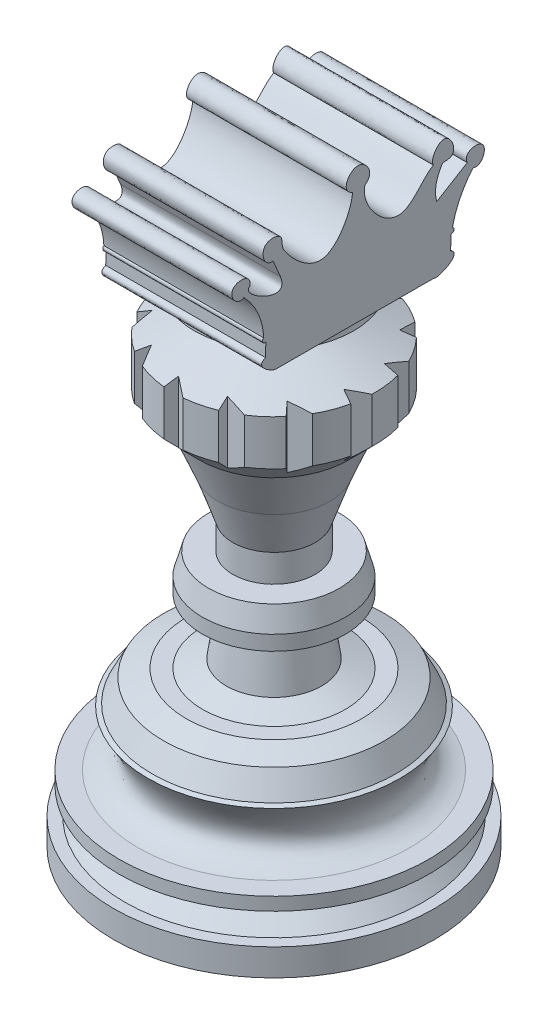
SolidWorks part; units mm, degrees
ref_plane "Front Plane" through (0, 0, 0) normal (0, 0, 1) x (1, 0, 0)
ref_plane "Top Plane" through (0, 0, 0) normal (0, 1, 0) x (1, 0, 0)
ref_plane "Right Plane" through (0, 0, 0) normal (1, 0, 0) x (0, 0, -1)
sketch "Sketch1" plane through (0, 0, 0) normal (0, 0, 1) x (1, 0, 0)
  line L0 (0, 80.19) -> (0, -88.5131)
  line L1 (0, -88.5131) -> (55.3807, -88.5131)
  line L2 (55.3807, -88.5131) -> (55.3807, -79.2296)
  line L3 (55.3807, -79.2296) -> (51.5393, -79.2296)
  line L4 (51.5393, -79.2296) -> (46.7375, -74.4278)
  line L5 (46.7375, -74.4278) -> (46.7375, -69.9461)
  line L6 (46.7375, -69.9461) -> (53.46, -69.9461)
  line L7 (53.46, -69.9461) -> (53.46, -65.4645)
  line L8 (53.46, -65.4645) -> (46.7375, -65.4645)
  line L9 (43.5363, -46.2573) -> (42.0663, -45.6507)
  line L10 (5.604, 73.2179) -> (27.4637, 79.3694)
  line L11 (27.4637, 79.3694) -> (27.217, 82.5705)
  line L12 (27.217, 82.5705) -> (5.6038, 80.19)
  line L13 (5.604, 73.2179) -> (11.7342, 67.0877)
  line L14 (11.7342, 67.0877) -> (16.6945, 72.0479)
  line L15 (16.6945, 72.0479) -> (34.7866, 64.5823)
  line L16 (34.7866, 64.5823) -> (34.7866, 48.9956)
  line L17 (34.7866, 48.9956) -> (25.7405, 39.9495)
  line L18 (25.7405, 39.9495) -> (19.3287, 24.411)
  line L19 (19.3287, 24.411) -> (14.2144, 9.5284)
  line L20 (14.2144, 9.5284) -> (14.2144, 0)
  line L21 (14.2142, -17.305) -> (16.411, -32.256)
  line L22 (16.411, -32.256) -> (24.6637, -35.092)
  line L23 (24.6637, -35.092) -> (30.2634, -35.092)
  line L24 (30.2634, -35.092) -> (38.0942, -37.7831)
  line L25 (38.0942, -37.7831) -> (42.0663, -45.6507)
  line L26 (14.2144, 0) -> (22.5344, 0)
  line L27 (22.5344, 0) -> (24.6637, -7.5667)
  line L28 (24.6637, -7.5667) -> (24.6637, -12.6453)
  line L29 (24.6637, -12.6453) -> (20.7635, -13.7428)
  line L30 (20.7635, -13.7428) -> (14.2142, -17.305)
  arc A0 (5.6038, 80.19) -> (0, 80.19) centre (2.8019, 79.5033) ccw
  spline S0 degree 3 poles (46.7375, -65.4645) (32.5271, -62.815) (39.1086, -52.8768) (43.5363, -46.2573) knots 0 0 0 0 1 1 1 1
revolve "Revolve6" add sketch "Sketch1" angle 360 about L0
sketch "Sketch8" plane through (0, 0, 0) normal (0, 1, 0) x (1, 0, 0)
  line L0 (-20.2346, 36.4498) -> (-5.043, 30.2682)
  line L1 (-5.043, 30.2682) -> (-5.043, 42.8457)
  line L2 (-5.043, 42.8457) -> (-20.2346, 36.4498)
extrude "Cut-Extrude2" cut sketch "Sketch8" along normal blind 169.926
pattern_circular "CirPattern3" count 13 over 360 about axis through (0, 64.5823, 0) along (0, 1, 0) of "Cut-Extrude2"
sketch "Sketch9" plane through (0, 0, 0) normal (1, 0, 0) x (0, 0, -1)
  line L0 (-6.1519, 164.3994) -> (167.1815, 164.3994) construction
  spline S0 degree 2 poles (40.719, 107.9744) (35.4591, 101.8044) (33.6322, 93.8008) knots 0 0 0 1 1 1
  spline S1 degree 2 poles (33.6322, 93.8008) (34.9835, 92.4777) (33.1545, 91.9694) knots 0 0 0 1 1 1
  spline S2 degree 1 poles (33.1545, 91.9694) (32.9937, 87.0415) knots 0 0 1 1
  spline S3 degree 3 poles (32.9937, 87.0415) (37.3893, 84.7994) (28.5998, 80.724) (27.0906, 81.7439) knots 0 0 0 0 1 1 1 1
  spline S4 degree 1 poles (27.0906, 81.7439) (-27.5309, 81.8647) knots 0 0 1 1
  spline S5 degree 3 poles (-27.5309, 81.8647) (-29.1171, 82.1606) (-34.7801, 85.5292) (-30.8793, 87.0965) knots 0 0 0 0 1 1 1 1
  spline S6 degree 1 poles (-30.8793, 87.0965) (-30.7537, 91.6586) knots 0 0 1 1
  spline S7 degree 3 poles (-30.7537, 91.6586) (-31.5066, 91.4175) (-32.1462, 92.3736) (-31.7321, 93.1499) (-31.5071, 93.291) knots 0 0 0 0 0.709491 1 1 1 1
  spline S8 degree 2 poles (-31.5071, 93.291) (-31.9253, 102.0684) (-38.3467, 108.7618) knots 0 0 0 1 1 1
  spline S9 degree 3 poles (-38.3467, 108.7618) (-40.7056, 107.2841) (-46.1552, 114.9998) (-35.5674, 115.2736) (-36.1981, 111.0872) knots 0 0 0 0 0.453037 1 1 1 1
  spline S10 degree 3 poles (-36.1981, 111.0872) (-40.4135, 109.3325) (-21.8039, 98.8056) (-25.7465, 108.7618) knots 0 0 0 0 1 1 1 1
  spline S11 degree 1 poles (-25.7465, 108.7618) (-28.2862, 114.7013) knots 0 0 1 1
  spline S12 degree 3 poles (-28.2862, 114.7013) (-31.3481, 113.9776) (-33.7191, 122.2578) (-24.3345, 121.4145) (-25.4364, 118.4594) (-24.7698, 116.4595) knots 0 0 0 0 0.455483 0.74807 1 1 1 1
  spline S13 degree 3 poles (-24.7698, 116.4595) (-22.6922, 112.7738) (-9.6601, 98.6892) (-0.9071, 117.303) (-0.8664, 121.4843) knots 0 0 0 0 0.479058 1 1 1 1
  spline S14 degree 3 poles (-0.8664, 121.4843) (-5.0571, 123.0415) (0.4096, 133.3963) (7.1585, 124.0057) (3.4592, 121.4843) knots 0 0 0 0 0.493893 1 1 1 1
  spline S15 degree 3 poles (3.4592, 121.4843) (1.7201, 115.7919) (15.325, 98.347) (23.772, 114.0401) (27.0906, 115.5804) knots 0 0 0 0 0.599093 1 1 1 1
  spline S16 degree 3 poles (27.0906, 115.5804) (25.701, 117.7117) (31.2608, 125.8045) (35.7405, 114.9364) (31.4281, 114.6987) (30.2829, 114.7013) knots 0 0 0 0 0.452983 0.806579 1 1 1 1
  spline S17 degree 2 poles (30.2829, 114.7013) (26.8135, 109.6455) (28.1682, 104.1372) knots 0 0 0 1 1 1
  spline S18 degree 1 poles (28.1682, 104.1372) (38.7202, 110.5332) knots 0 0 1 1
  spline S19 degree 3 poles (38.7202, 110.5332) (37.0458, 114.0936) (47.5797, 116.1949) (43.7642, 106.7958) (40.719, 107.9744) knots 0 0 0 0 0.508239 1 1 1 1
extrude "Boss-Extrude1" add sketch "Sketch9" along normal blind 27.94 and the other way blind 27.178
extrude "Boss-Extrude2" add sketch "Sketch9<2>" along normal blind 23.114
sketch "Sketch9<2>" plane through (0, 0, 0) normal (1, 0, 0) x (0, 0, -1) same geometry as "Sketch9"
